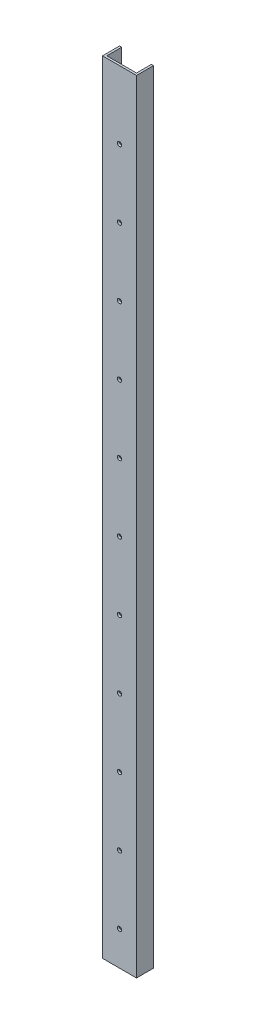
SolidWorks part; units mm, degrees
ref_plane "Front" through (0, 0, 0) normal (0, 0, 1) x (1, 0, 0)
ref_plane "Top" through (0, 0, 0) normal (0, 1, 0) x (1, 0, 0)
ref_plane "Right" through (0, 0, 0) normal (1, 0, 0) x (0, 0, -1)
sketch "Sketch1" plane through (0, 0, 0) normal (0, 1, 0) x (1, 0, 0)
  line L0 (3.175, 3.175) -> (3.175, 25.4)
  line L1 (0, 0) -> (50.8, 0)
  line L2 (0, 0) -> (0, 25.4)
  line L4 (50.8, 0) -> (50.8, 25.4)
  line L5 (3.175, 3.175) -> (47.625, 3.175)
  line L6 (47.625, 3.175) -> (47.625, 25.4)
  line L7 (0, 25.4) -> (3.175, 25.4)
  line L8 (50.8, 25.4) -> (47.625, 25.4)
  dimension "D1" = 25.4
  dimension "D2" = 50.8
  dimension "D3" = 3.175
extrude "Boss-Extrude1" add sketch "Sketch1" along normal blind 1168.4
sketch "Sketch2" plane through (0, 0, 0) normal (0, 0, 1) x (1, 0, 0)
  line L0 (25.4, 0) -> (25.4, 50.8) construction
  line L1 (0, 0) -> (50.8, 0) construction
  circle A0 centre (25.4, 50.8) radius 3.175
  circle A1 centre (25.4, 152.4) radius 3.175
  circle A2 centre (25.4, 254) radius 3.175
  circle A3 centre (25.4, 355.6) radius 3.175
  circle A4 centre (25.4, 457.2) radius 3.175
  circle A5 centre (25.4, 558.8) radius 3.175
  circle A6 centre (25.4, 660.4) radius 3.175
  circle A7 centre (25.4, 762) radius 3.175
  circle A8 centre (25.4, 863.6) radius 3.175
  circle A9 centre (25.4, 965.2) radius 3.175
  circle A10 centre (25.4, 1066.8) radius 3.175
  dimension "D2" = 6.35
  dimension "D1" = 50.8
  dimension "D3" = 11
extrude "Cut-Extrude1" cut sketch "Sketch2" against normal up to next
